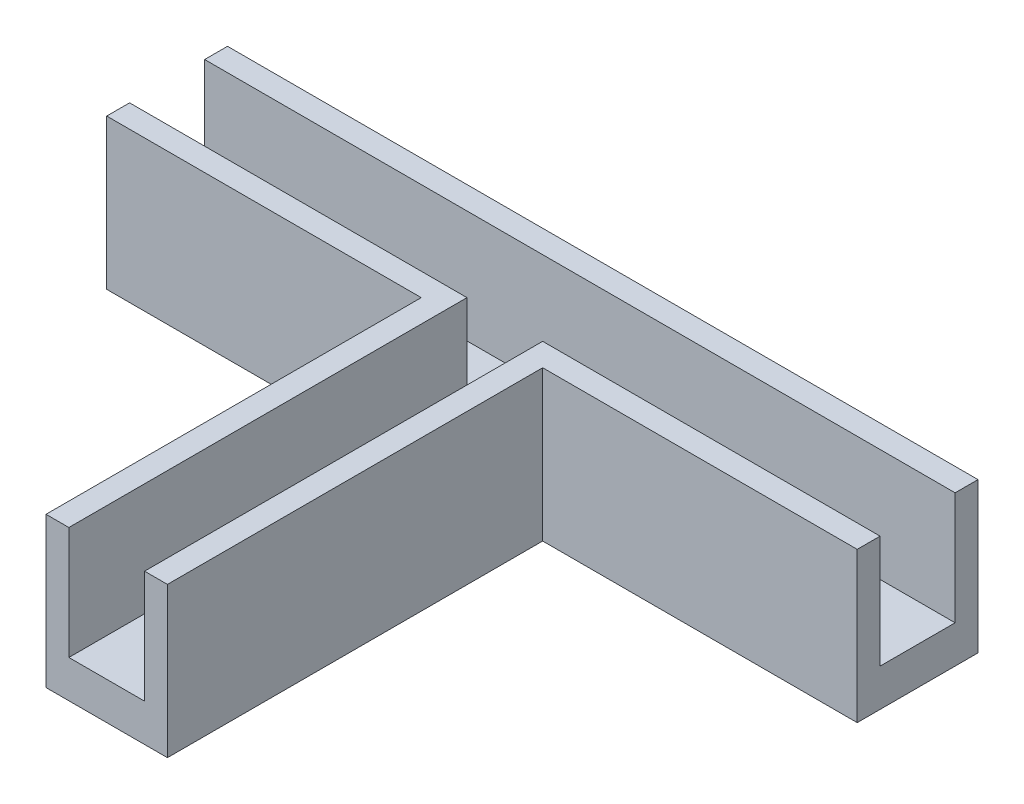
SolidWorks part; units mm, degrees
ref_plane "Front Plane" through (0, 0, 0) normal (0, 0, 1) x (1, 0, 0)
ref_plane "Top Plane" through (0, 0, 0) normal (0, 1, 0) x (1, 0, 0)
ref_plane "Right Plane" through (0, 0, 0) normal (1, 0, 0) x (0, 0, -1)
sketch "Sketch1" plane through (0, 0, 0) normal (0, 1, 0) x (1, 0, 0)
  line L1 (-25, 2.5) -> (25, 2.5)
  line L2 (-25, 2.5) -> (-25, -2.5)
  line L3 (-25, -2.5) -> (25, -2.5)
  line L4 (25, 2.5) -> (25, -2.5)
  line L5 (-25, 2.5) -> (25, -2.5) construction
  line L6 (-25, -2.5) -> (25, 2.5) construction
  line L7 (-25, 2.5) -> (25, 2.5)
  line L8 (-25, 2.5) -> (-25, 4.024)
  line L9 (-25, 4.024) -> (25, 4.024)
  line L10 (25, 2.5) -> (25, 4.024)
  line L11 (-25, -2.5) -> (-2.521, -2.5)
  line L12 (-25, -2.5) -> (-25, -4.024)
  line L13 (-25, -4.024) -> (-2.521, -4.024)
  line L14 (-2.521, -2.5) -> (-2.521, -4.024)
  line L15 (25, -2.5) -> (2.521, -2.5)
  line L16 (25, -2.5) -> (25, -4.024)
  line L17 (25, -4.024) -> (2.521, -4.024)
  line L18 (2.521, -2.5) -> (2.521, -4.024)
  line L19 (-2.521, -4.024) -> (-4.045, -4.024)
  line L20 (-2.521, -4.024) -> (-2.521, -29.024)
  line L21 (-2.521, -29.024) -> (-4.045, -29.024)
  line L22 (-4.045, -4.024) -> (-4.045, -29.024)
  line L23 (2.521, -4.024) -> (4.045, -4.024)
  line L24 (2.521, -4.024) -> (2.521, -29.024)
  line L25 (2.521, -29.024) -> (4.045, -29.024)
  line L26 (4.045, -4.024) -> (4.045, -29.024)
  line L27 (-2.521, -2.5) -> (2.521, -2.5)
  line L28 (-2.521, -2.5) -> (-2.521, -29.024)
  line L29 (-2.521, -29.024) -> (2.521, -29.024)
  line L30 (2.521, -2.5) -> (2.521, -29.024)
  point P0 (0, 0)
  dimension "D1" = 5
  dimension "D2" = 1.524
  dimension "D3" = 50
  dimension "D4" = 22.479
  dimension "D5" = 22.479
  dimension "D6" = 25
  dimension "D7" = 25
  dimension "D8" = 1.524
  dimension "D9" = 1.524
  dimension "D10" = 1.524
extrude "Boss-Extrude1" add sketch "Sketch1" along normal blind 2.5 contours L20 L29 L24 L18 L3 L14 region at (0, 0, 15.762)
extrude "Boss-Extrude2" add sketch "Sketch1<5>" along normal blind 2.5 contours L4 L1 L2 L3 region at (0, 0, 0)
sketch "Sketch1<5>" plane through (0, 0, 0) normal (0, 1, 0) x (1, 0, 0) same geometry as "Sketch1"
extrude "Boss-Extrude3" add sketch "Sketch1<6>" along normal blind 10 contours L3 L18 L17 L16 | L1 L10 L9 L8 | L26 L17 L24 L25 | L13 L22 L21 L20 | L14 L3 L12 L13 region at (0, 0, -3.262) region at (-13.7605, 0, 3.262) region at (13.7605, 0, 3.262) region at (-3.283, 0, 16.524) region at (3.283, 0, 16.524)
sketch "Sketch1<6>" plane through (0, 0, 0) normal (0, 1, 0) x (1, 0, 0) same geometry as "Sketch1"
